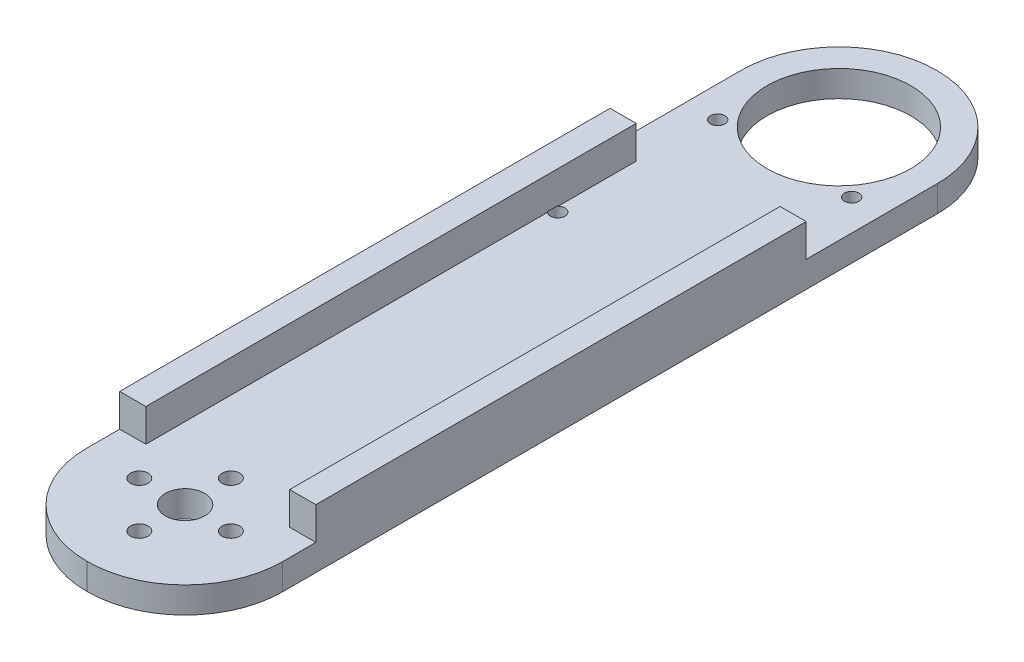
SolidWorks part; units mm, degrees
ref_plane "Front Plane" through (0, 0, 0) normal (0, 0, 1) x (1, 0, 0)
ref_plane "Top Plane" through (0, 0, 0) normal (0, 1, 0) x (1, 0, 0)
ref_plane "Right Plane" through (0, 0, 0) normal (1, 0, 0) x (0, 0, -1)
ref_plane "PY_p18_625" through (0, 18.625, 0) normal (0, 1, 0) x (1, 0, 0)
sketch "S_prism1" plane through (0, 18.625, 0) normal (0, 1, 0) x (1, 0, 0)
  line L0 (-0.1, -15) -> (0.1, -15)
  line L1 (15, -0.1) -> (15, 100.1)
  line L2 (0.1, 115) -> (-0.1, 115)
  line L3 (-15, 100.1) -> (-15, -0.1)
  arc A0 (-15, -0.1) -> (-0.1, -15) centre (-0.1, -0.1) ccw
  arc A1 (0.1, -15) -> (15, -0.1) centre (0.1, -0.1) ccw
  arc A2 (15, 100.1) -> (0.1, 115) centre (0.1, 100.1) ccw
  arc A3 (-0.1, 115) -> (-15, 100.1) centre (-0.1, 100.1) ccw
extrude "Boss_1" add sketch "S_prism1" along normal blind 4
ref_plane "PZ_m80_000" through (0, 0, -80) normal (0, 0, 1) x (1, 0, 0)
sketch "S_box2" plane through (0, 0, -80) normal (0, 0, 1) x (1, 0, 0)
  line L0 (-15, 22.125) -> (-11, 22.125)
  line L1 (-11, 22.125) -> (-11, 27.625)
  line L2 (-11, 27.625) -> (-15, 27.625)
  line L3 (-15, 27.625) -> (-15, 22.125)
  dimension "P1" = 15
  dimension "P2" = 22.125
  dimension "P3" = 11
  dimension "P4" = 22.125
  dimension "P5" = 11
  dimension "P6" = 27.625
  dimension "P7" = 15
  dimension "P8" = 27.625
extrude "Boss_2" add sketch "S_box2" along normal blind 75
sketch "S_box3" plane through (0, 0, -80) normal (0, 0, 1) x (1, 0, 0)
  line L0 (11, 22.125) -> (15, 22.125)
  line L1 (15, 22.125) -> (15, 27.625)
  line L2 (15, 27.625) -> (11, 27.625)
  line L3 (11, 27.625) -> (11, 22.125)
  dimension "P1" = 11
  dimension "P2" = 22.125
  dimension "P3" = 15
  dimension "P4" = 22.125
  dimension "P5" = 15
  dimension "P6" = 27.625
  dimension "P7" = 11
  dimension "P8" = 27.625
extrude "Boss_3" add sketch "S_box3" along normal blind 75
ref_plane "PY_p18_525" through (0, 18.525, 0) normal (0, 1, 0) x (1, 0, 0)
sketch "S_hole4" plane through (0, 18.525, 0) normal (0, 1, 0) x (1, 0, 0)
  circle A0 centre (0, 0) radius 3
  dimension "D1_S_hole4" = 6
extrude "Hole_4" cut sketch "S_hole4" along normal blind 4.2
sketch "S_hole5" plane through (0, 18.525, 0) normal (0, 1, 0) x (1, 0, 0)
  circle A0 centre (7, 0) radius 1.35
  dimension "D1_S_hole5" = 2.7
  dimension "P2" = 7
extrude "Hole_5" cut sketch "S_hole5" along normal blind 4.2
sketch "S_hole6" plane through (0, 18.525, 0) normal (0, 1, 0) x (1, 0, 0)
  circle A0 centre (0, -7) radius 1.35
  dimension "D1_S_hole6" = 2.7
  dimension "P2" = 7
extrude "Hole_6" cut sketch "S_hole6" along normal blind 4.2
sketch "S_hole7" plane through (0, 18.525, 0) normal (0, 1, 0) x (1, 0, 0)
  circle A0 centre (-7, 0) radius 1.35
  dimension "D1_S_hole7" = 2.7
  dimension "P2" = 7
extrude "Hole_7" cut sketch "S_hole7" along normal blind 4.2
sketch "S_hole8" plane through (0, 18.525, 0) normal (0, 1, 0) x (1, 0, 0)
  circle A0 centre (0, 7) radius 1.35
  dimension "D1_S_hole8" = 2.7
  dimension "P2" = 7
extrude "Hole_8" cut sketch "S_hole8" along normal blind 4.2
sketch "S_hole9" plane through (0, 18.525, 0) normal (0, 1, 0) x (1, 0, 0)
  circle A0 centre (0, 100) radius 11
  dimension "D1_S_hole9" = 22
  dimension "P2" = 100
extrude "Hole_9" cut sketch "S_hole9" along normal blind 4.2
sketch "S_hole10" plane through (0, 18.525, 0) normal (0, 1, 0) x (1, 0, 0)
  circle A0 centre (-10.25, 91.7) radius 1.1
  dimension "D1_S_hole10" = 2.2
  dimension "P2" = 10.25
  dimension "P3" = 91.7
extrude "Hole_10" cut sketch "S_hole10" along normal blind 4.2
sketch "S_hole11" plane through (0, 18.525, 0) normal (0, 1, 0) x (1, 0, 0)
  circle A0 centre (10.25, 91.7) radius 1.1
  dimension "D1_S_hole11" = 2.2
  dimension "P2" = 10.25
  dimension "P3" = 91.7
extrude "Hole_11" cut sketch "S_hole11" along normal blind 4.2
sketch "S_hole12" plane through (0, 18.525, 0) normal (0, 1, 0) x (1, 0, 0)
  circle A0 centre (-10.25, 67.25) radius 1.1
  dimension "D1_S_hole12" = 2.2
  dimension "P2" = 10.25
  dimension "P3" = 67.25
extrude "Hole_12" cut sketch "S_hole12" along normal blind 4.2
sketch "S_hole13" plane through (0, 18.525, 0) normal (0, 1, 0) x (1, 0, 0)
  circle A0 centre (10.25, 67.25) radius 1.1
  dimension "D1_S_hole13" = 2.2
  dimension "P2" = 10.25
  dimension "P3" = 67.25
extrude "Hole_13" cut sketch "S_hole13" along normal blind 4.2
equation "\"plate_t\" = 3"
equation "\"clearance\" = 0.4"
